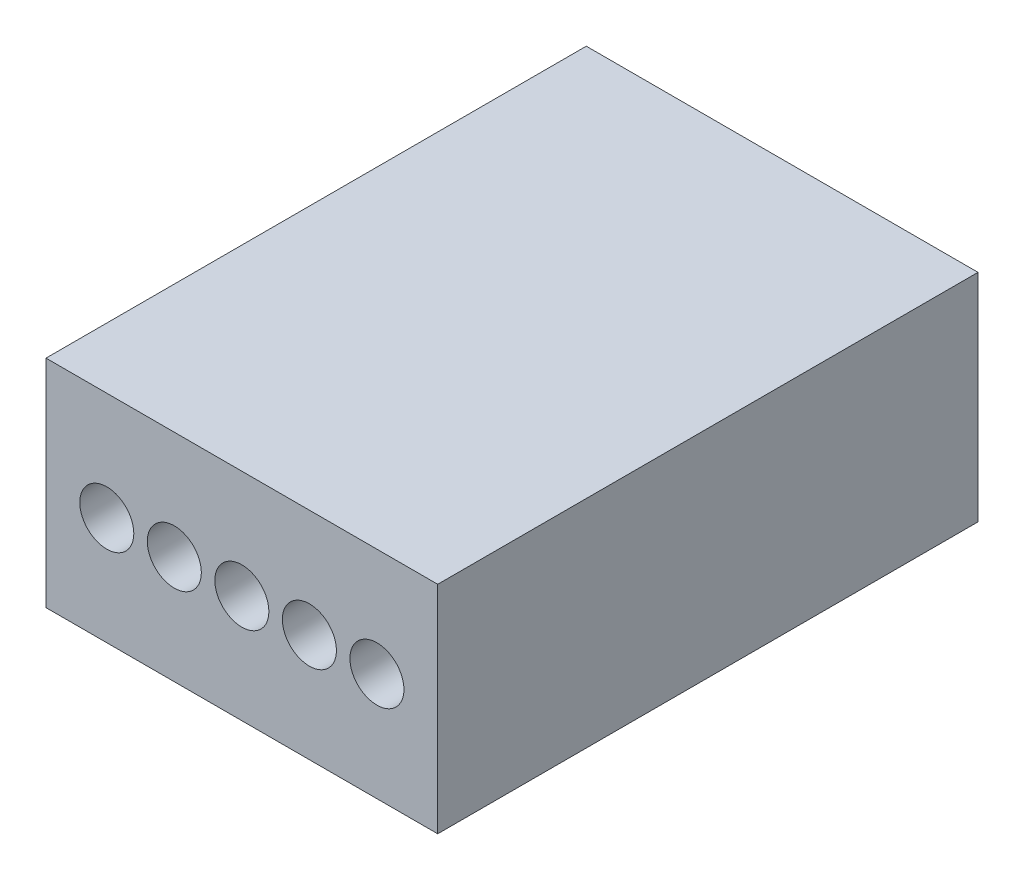
SolidWorks part; units mm, degrees
ref_plane "Front Plane" through (0, 0, 0) normal (0, 0, 1) x (1, 0, 0)
ref_plane "Top Plane" through (0, 0, 0) normal (0, 1, 0) x (1, 0, 0)
ref_plane "Right Plane" through (0, 0, 0) normal (1, 0, 0) x (0, 0, -1)
sketch "Sketch2" plane through (0, 0, 0) normal (0, 0, 1) x (1, 0, 0)
  line L1 (0, 0) -> (7.25, 0)
  line L2 (0, 0) -> (0, 4)
  line L3 (0, 4) -> (7.25, 4)
  line L4 (7.25, 0) -> (7.25, 4)
  dimension "D1" = 7.25
  dimension "D2" = 4
extrude "Boss-Extrude1" add sketch "Sketch2" along normal blind 10
sketch "Sketch3" plane through (0, 0, 10) normal (0, 0, 1) x (1, 0, 0)
  line L0 (0, 2) -> (7.25, 2) construction
  line L1 (0, 4) -> (0, 0) construction
  line L2 (7.25, 0) -> (7.25, 4) construction
  line L3 (0, 2) -> (7.25, 2) construction
  line L4 (7.25, 4) -> (0, 4) construction
  line L5 (0, 0) -> (7.25, 0) construction
  line L6 (1.125, 4) -> (1.125, 0) construction
  circle A0 centre (1.125, 2) radius 0.5
  circle A1 centre (2.375, 2) radius 0.5
  circle A2 centre (3.625, 2) radius 0.5
  circle A3 centre (4.875, 2) radius 0.5
  circle A4 centre (6.125, 2) radius 0.5
  circle A21 centre (24.875, 2) radius 0.5 [skipped]
  circle A22 centre (23.625, 2) radius 0.5 [skipped]
  circle A23 centre (22.375, 2) radius 0.5 [skipped]
  circle A24 centre (21.125, 2) radius 0.5 [skipped]
  circle A25 centre (19.875, 2) radius 0.5 [skipped]
  circle A26 centre (18.625, 2) radius 0.5 [skipped]
  circle A27 centre (17.375, 2) radius 0.5 [skipped]
  circle A28 centre (16.125, 2) radius 0.5 [skipped]
  circle A29 centre (14.875, 2) radius 0.5 [skipped]
  circle A30 centre (13.625, 2) radius 0.5 [skipped]
  circle A31 centre (12.375, 2) radius 0.5 [skipped]
  circle A32 centre (11.125, 2) radius 0.5 [skipped]
  circle A33 centre (9.875, 2) radius 0.5 [skipped]
  circle A34 centre (7.375, 2) radius 0.5 [skipped]
  circle A35 centre (8.625, 2) radius 0.5 [skipped]
  dimension "D1" = 1
  dimension "D2" = 2
  dimension "D3" = 1.125
  dimension "D5" = 1.25
  dimension "D4" = 20
extrude "Cut-Extrude1" cut sketch "Sketch3" against normal blind 5
sketch "Sketch4" plane through (0, 0, 10) normal (0, 0, 1) x (1, 0, 0)
  point P0 (1.125, 2)
  point P1 (2.375, 2)
  point P3 (3.625, 2)
  point P5 (4.875, 2)
  point P7 (6.125, 2)
other "CPoint1" parameters "Diameter"=25.4, "StubLength"=38.1
ref_axis "Axis1" through (1.125, 2, 20) along (0, 0, -1)
other "CPoint2" parameters "Diameter"=25.4, "StubLength"=38.1
ref_axis "Axis2" through (2.375, 2, 20) along (0, 0, -1)
other "CPoint3" parameters "Diameter"=25.4, "StubLength"=38.1
ref_axis "Axis3" through (3.625, 2, 20) along (0, 0, -1)
other "CPoint4" parameters "Diameter"=25.4, "StubLength"=38.1
ref_axis "Axis4" through (4.875, 2, 20) along (0, 0, -1)
other "CPoint5" parameters "Diameter"=25.4, "StubLength"=38.1
ref_axis "Axis5" through (6.125, 2, 20) along (0, 0, -1)
